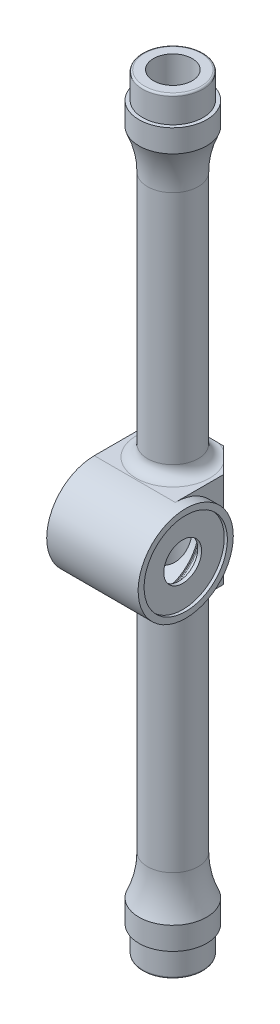
SolidWorks part; units mm, degrees
material "6061 Alloy"
ref_plane "X-Y Datum" through (0, 0, 0) normal (0, 0, 1) x (1, 0, 0)
ref_plane "X-Z Datum" through (0, 0, 0) normal (0, 1, 0) x (1, 0, 0)
ref_plane "Y-Z Datum" through (0, 0, 0) normal (1, 0, 0) x (0, 0, -1)
sketch "Sketch1" plane through (0, 0, 0) normal (1, 0, 0) x (0, 0, -1)
  line L1 (-16.002, -20.0025) -> (14.732, -20.0025)
  line L2 (14.732, -20.0025) -> (14.732, 20.0025)
  line L3 (14.732, 20.0025) -> (-16.002, 20.0025)
  line L4 (-16.002, -20.0025) -> (-16.002, 20.0025) construction
  circle A0 centre (-16.002, 0) radius 20.0025
  dimension "D1" = 40.005
  dimension "D2" = 16.002
  dimension "D3" = 30.734
extrude "Boss-Extrude1" add sketch "Sketch1" along normal mid plane 34.036 contours A0 L1 L2 L3 region at (0, 0, -6.5566)
extrude "Boss-Extrude2" add sketch "Sketch2<3>" against normal blind 17.018 and the other way blind 21.4122 contours L4 A0 | L4 A0 region at (0, 0, 24.4913) region at (0, 0, 7.5127)
sketch "Sketch2<3>" plane through (0, 0, 0) normal (1, 0, 0) x (0, 0, -1) same geometry as "Sketch1"
sketch "Sketch4" plane through (0, 0, 0) normal (1, 0, 0) x (0, 0, -1)
  line L0 (0, 220.98) -> (0, -220.98) construction
  line L1 (-8.128, -161.036) -> (-8.128, 161.036)
  line L2 (-1000, 0) -> (49000, 0) construction
  line L3 (-8.128, -161.036) -> (-11.938, -161.036)
  line L4 (-12.7, -160.274) -> (-12.7, -149.9235)
  line L5 (-12.7, -149.9235) -> (-14.224, -149.9235)
  line L6 (-14.224, -149.9235) -> (-14.224, -140.3985)
  line L7 (-10.668, -123.7736) -> (-10.668, -24.765)
  line L8 (-16.002, -20.0025) -> (14.732, -20.0025) construction
  line L9 (-15.4305, -20.0025) -> (-15.4305, 20.0025)
  line L11 (-10.668, 123.7736) -> (-10.668, 24.765)
  line L12 (-14.224, 149.9235) -> (-14.224, 140.3985)
  line L13 (-12.7, 149.9235) -> (-14.224, 149.9235)
  line L14 (-12.7, 160.274) -> (-12.7, 149.9235)
  line L15 (-8.128, 161.036) -> (-11.938, 161.036)
  arc A0 (-10.668, -123.7736) -> (-14.224, -140.3985) centre (-51.308, -123.7736) cw
  arc A1 (-12.7, -160.274) -> (-11.938, -161.036) centre (-11.938, -160.274) ccw
  arc A2 (-10.668, -24.765) -> (-15.4305, -20.0025) centre (-15.4305, -24.765) ccw
  arc A3 (-10.668, 24.765) -> (-15.4305, 20.0025) centre (-15.4305, 24.765) cw
  arc A4 (-12.7, 160.274) -> (-11.938, 161.036) centre (-11.938, 160.274) cw
  arc A5 (-10.668, 123.7736) -> (-14.224, 140.3985) centre (-51.308, 123.7736) ccw
  point P4 (0, 0)
  point P31 (-15.4305, 0)
  point P34 (-8.128, 0)
  dimension "D4" = 0.762
  dimension "D6" = 40.64
  dimension "D11" = 4.7625
  dimension "D2" = 16.256
  dimension "D3" = 2.54
  dimension "D5" = 3.81
  dimension "D7" = 6.096
  dimension "D8" = 9.525
  dimension "D9" = 59.944
  dimension "D10" = 11.1125
  dimension "D12" = 441.96
revolve "Rack Housing Revolve" add sketch "Sketch4" angle 360 about L0
sketch "Sketch2" plane through (0, 0, 0) normal (0, 1, 0) x (1, 0, 0)
  line L0 (21.4122, -36.0045) -> (21.4122, 4.0005) construction
  line L1 (21.4122, -36.0045) -> (21.4122, 4.0005) construction
  line L2 (21.4122, -16.002) -> (-17.018, -16.002) construction
  line L3 (-17.018, -16.002) -> (-17.018, 14.732) construction
  line L4 (-17.018, -16.002) -> (-17.018, -26.67)
  line L5 (-17.018, -16.002) -> (-17.018, -36.0045) construction
  line L6 (-17.018, -26.67) -> (-15.5448, -26.67)
  line L7 (-15.5448, -26.67) -> (-15.5448, -27.686)
  line L8 (-15.2273, -28.0035) -> (-10.541, -28.0035)
  line L9 (-10.541, -28.0035) -> (-10.541, -32.4993)
  line L10 (-10.541, -32.4993) -> (10.541, -32.4993)
  line L11 (10.541, -32.4993) -> (10.541, -33.1851)
  line L12 (10.8585, -33.5026) -> (18.542, -33.5026)
  line L13 (18.542, -33.5026) -> (18.542, -23.9395)
  line L14 (18.542, -23.9395) -> (20.1295, -23.9395)
  line L15 (20.1295, -23.9395) -> (20.1295, -33.5026)
  line L16 (20.1295, -33.5026) -> (21.4122, -33.5026)
  line L17 (21.4122, -33.5026) -> (21.4122, -16.002)
  line L18 (-17.018, -16.002) -> (21.4122, -16.002)
  arc A0 (10.8585, -33.5026) -> (10.541, -33.1851) centre (10.8585, -33.1851) cw
  arc A1 (-15.2273, -28.0035) -> (-15.5448, -27.686) centre (-15.2273, -27.686) cw
  point P25 (0, -32.4993)
  dimension "D1" = 0.3175
  dimension "D2" = 1.5875
  dimension "D3" = 8.001
  dimension "D4" = 21.336
  dimension "D5" = 24.003
  dimension "D6" = 32.9946
  dimension "D7" = 35.0012
  dimension "D8" = 15.875
  dimension "D9" = 21.082
  dimension "D10" = 5.0038
revolve "Pinion Revolve Cut" cut sketch "Sketch2" angle 360 about L18
sketch "Sketch5" plane through (0, 0, 0) normal (0, 1, 0) x (1, 0, 0)
  circle A0 centre (0, 0) radius 8.128 construction
  circle A1 centre (0, 0) radius 8.128
extrude "Rack Clearance Hole" cut sketch "Sketch5" against normal through all both and the other way through all
sketch "Sketch6" plane through (0, 0, 0) normal (0, 1, 0) x (1, 0, 0)
  line L0 (-6.604, 14.732) -> (6.604, 14.732)
  line L1 (17.018, 14.732) -> (4.59, 14.732) construction
  line L2 (-6.604, 14.732) -> (-17.018, 4.318)
  line L3 (-17.018, -16.002) -> (-17.018, 14.732) construction
  line L4 (-17.018, 4.318) -> (-17.018, 14.732)
  line L5 (-17.018, 14.732) -> (-6.604, 14.732) construction
  line L6 (6.604, 14.732) -> (17.018, 4.318)
  line L7 (17.018, -16.002) -> (17.018, 14.732) construction
  line L8 (17.018, 4.318) -> (17.018, 14.732)
  line L9 (17.018, 14.732) -> (6.604, 14.732) construction
  line L10 (-17.018, 14.732) -> (-17.018, 17.907)
  line L11 (-17.018, 17.907) -> (17.018, 17.907)
  line L12 (17.018, 17.907) -> (17.018, 14.732)
  point P5 (0, 14.732)
  dimension "D1" = 13.208
  dimension "D2" = 45
  dimension "D3" = 45
  dimension "D4" = 3.175
extrude "Body Chamfer" cut sketch "Sketch6" against normal mid plane 50.8 contours L12 L8 L6 L0 L2 L4 L10 L11
equation "\"D12@Sketch4\" = 17.4in"
